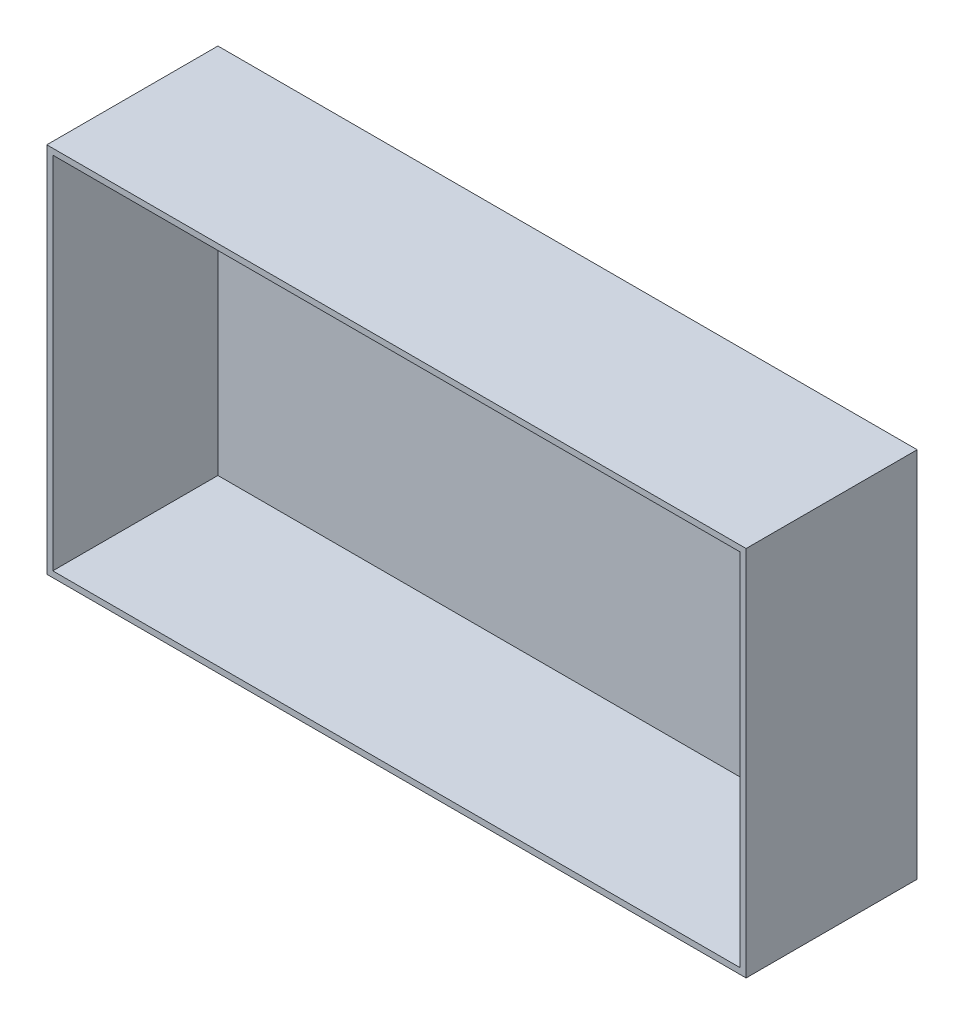
SolidWorks part; units mm, degrees
ref_plane "Plan de face" through (0, 0, 0) normal (0, 0, 1) x (1, 0, 0)
ref_plane "Plan de dessus" through (0, 0, 0) normal (0, 1, 0) x (1, 0, 0)
ref_plane "Plan de droite" through (0, 0, 0) normal (1, 0, 0) x (0, 0, -1)
sketch "Esquisse1" plane through (0, 0, 0) normal (0, 0, 1) x (1, 0, 0)
  line L1 (-47, 25) -> (47, 25)
  line L2 (-47, 25) -> (-47, -25)
  line L3 (-47, -25) -> (47, -25)
  line L4 (47, 25) -> (47, -25)
  line L5 (-47, 25) -> (47, -25) construction
  line L6 (-47, -25) -> (47, 25) construction
  point P0 (0, 0)
  dimension "D1" = 94
  dimension "D2" = 50
extrude "Boss.-Extru.1" add sketch "Esquisse1" along normal blind 23
shell "Coque1" thickness 0.8 removed face at (0, 0, 23)
equation "\"buse\"= 0.8"
equation "\"D1@Coque1\"=\"buse\""
